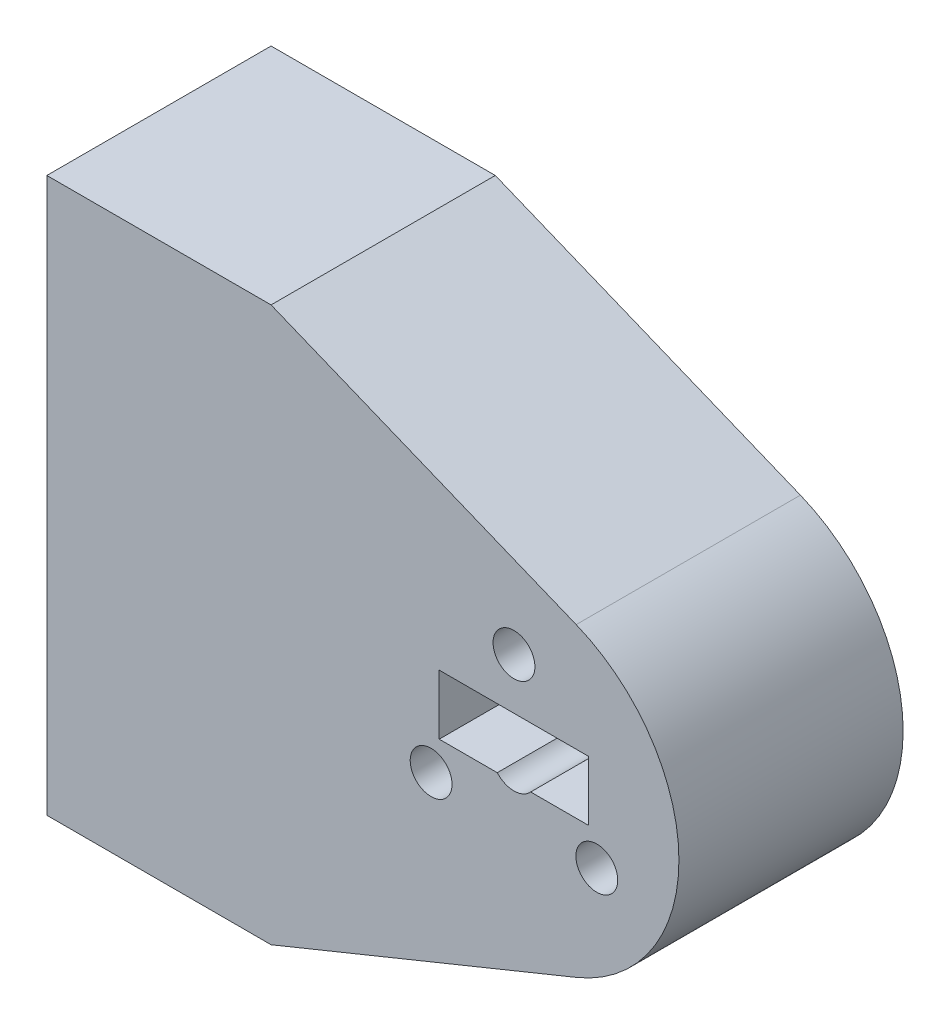
SolidWorks part; units mm, degrees
ref_plane "정면" through (0, 0, 0) normal (0, 0, 1) x (1, 0, 0)
ref_plane "윗면" through (0, 0, 0) normal (0, 1, 0) x (1, 0, 0)
ref_plane "우측면" through (0, 0, 0) normal (1, 0, 0) x (0, 0, -1)
sketch "스케치1" plane through (0, 0, 0) normal (0, 0, 1) x (1, 0, 0)
  line L0 (0, 0) -> (0, 33.5972) construction
  line L1 (0, 0) -> (-11.0851, -6.4) construction
  line L7 (10, 6) -> (-10, 6)
  line L8 (10, 6) -> (10, -2)
  line L9 (10, -2) -> (-10, -2)
  line L10 (-10, 6) -> (-10, -2)
  line L11 (10, 6) -> (-10, -2) construction
  line L12 (10, -2) -> (-10, 6) construction
  circle A0 centre (0, 0) radius 22.0716
  circle A1 centre (0, 12.8) radius 2.8
  circle A2 centre (0, 0) radius 15.95
  circle A3 centre (11.0851, -6.4) radius 2.8
  circle A4 centre (-11.0851, -6.4) radius 2.8
  circle A5 centre (0, 0) radius 3
  point P0 (0, 2)
  point P14 (0, 0)
  dimension "D1" = 5.6
  dimension "D2" = 31.9
  dimension "D3" = 44.1433
  dimension "D4" = 12.8
  dimension "D6" = 20
  dimension "D7" = 8
  dimension "D9" = 6
  dimension "D10" = 5.6
  dimension "D11" = 5.6
  dimension "D8" = 2
  dimension "D5" = 3
extrude "보스-돌출1" add sketch "스케치1" along normal blind 5 contours A1 A2 A4 A3 | A2 A0 region at (-21.4474, 0, 0) region at (-15.4989, 0, 0)
sketch "스케치2" plane through (0, 0, 0) normal (0, 0, 1) x (1, 0, 0)
  line L0 (0, 0) -> (-62.5, 0) construction
  line L1 (0, 22.0716) -> (-62.5, 22.0716)
  line L2 (-62.5, 22.0716) -> (-62.5, -22.0716)
  line L3 (-62.5, -22.0716) -> (0, -22.0716)
  line L4 (-45.5, 33.3049) -> (-45.5, -54.0151) construction
  line L5 (-62.5, -22.0716) -> (-62.5, -37.0716)
  line L6 (-62.5, -37.0716) -> (-32.5, -37.0716)
  line L7 (-32.5, -37.0716) -> (8.3266, -20.4408)
  line L8 (-45.5, -33.3049) -> (-45.5, 54.0151) construction
  line L9 (-32.5, 37.0716) -> (8.3266, 20.4408)
  line L10 (-62.5, 37.0716) -> (-32.5, 37.0716)
  line L11 (-62.5, 22.0716) -> (-62.5, 37.0716)
  line L12 (-10, 6) -> (-10, -2)
  line L13 (-10, 6) -> (-10, -2)
  line L14 (-2.2361, -2) -> (-10, -2)
  line L15 (-2.2361, -2) -> (-10, -2)
  line L16 (10, -2) -> (2.2361, -2)
  line L17 (10, -2) -> (2.2361, -2)
  line L18 (10, 6) -> (10, -2)
  line L19 (10, 6) -> (10, -2)
  line L20 (10, 6) -> (-10, 6)
  line L21 (10, 6) -> (-10, 6)
  circle A1 centre (0, 0) radius 22.0716
  circle A2 centre (0, 0) radius 22.0716
  circle A3 centre (0, 12.8) radius 2.8
  circle A4 centre (0, 12.8) radius 2.8
  circle A5 centre (-11.0851, -6.4) radius 2.8
  circle A6 centre (-11.0851, -6.4) radius 2.8
  arc A7 (-2.2361, -2) -> (2.2361, -2) centre (0, 0) ccw
  arc A8 (-2.2361, -2) -> (2.2361, -2) centre (0, 0) ccw
  circle A9 centre (11.0851, -6.4) radius 2.8
  circle A10 centre (11.0851, -6.4) radius 2.8
  point P12 (-45.5, 0)
  dimension "D5" = 15
  dimension "D6" = 30
  dimension "D2" = 44.1433
  dimension "D3" = 62.5
  dimension "D4" = 17
  dimension "D1" = 0
extrude "보스-돌출2" add sketch "스케치2" along normal blind 30 contours A2 L3 L5 L6 L7 | A2 L1 L2 L3 | A2 A10 A8 L15 L13 L21 L19 L17 A6 A4 | A2 L9 L10 L11 L1 region at (-39.6488, 0, 0) region at (-37.0594, 28.6096, 0) region at (4.1224, 21.0474, 0) region at (-37.0594, -28.6096, 0)
sketch "스케치3" plane through (0, 0, 0) normal (0, 0, 1) x (1, 0, 0)
  line L5 (-32.5, -37.0716) -> (8.3266, -20.4408)
  line L6 (-62.5, -37.0716) -> (-32.5, -37.0716)
  line L7 (-62.5, 37.0716) -> (-62.5, -37.0716)
  line L8 (-32.5, 37.0716) -> (-62.5, 37.0716)
  line L9 (8.3266, 20.4408) -> (-32.5, 37.0716)
  line L10 (-32.5, -37.0716) -> (8.3266, -20.4408)
  line L11 (-62.5, -37.0716) -> (-32.5, -37.0716)
  line L12 (-62.5, 37.0716) -> (-62.5, -37.0716)
  line L13 (-32.5, 37.0716) -> (-62.5, 37.0716)
  line L14 (8.3266, 20.4408) -> (-32.5, 37.0716)
  circle A0 centre (0, 12.8) radius 2.8
  arc A1 (8.3266, -20.4408) -> (8.3266, 20.4408) centre (0, 0) ccw
  arc A2 (8.3266, -20.4408) -> (8.3266, 20.4408) centre (0, 0) ccw
  circle A3 centre (0, 12.8) radius 2.8
  circle A4 centre (-11.0851, -6.4) radius 2.8
  circle A5 centre (-11.0851, -6.4) radius 2.8
  circle A6 centre (11.0851, -6.4) radius 2.8
  circle A7 centre (11.0851, -6.4) radius 2.8
  circle A8 centre (0, 12.8) radius 5
  circle A9 centre (11.0851, -6.4) radius 5
  circle A10 centre (-11.0851, -6.4) radius 5
  dimension "D2" = 10
  dimension "D3" = 10
  dimension "D4" = 10
  dimension "D1" = 0
extrude "컷-돌출1" cut sketch "스케치3" along normal blind 10 contours A9 A7 | A8 A3 | A10 A5 region at (-4.8586, 12.8, 0) region at (6.2265, -6.4, 0) region at (-15.9437, -6.4, 0)
fillet "필렛2" radius 2 4 edges at (8.7103, -2, 5) (10, -1.5192, 5) (10, -1.7596, 10) (9.3551, -2, 10)
fillet "필렛3" radius 2 4 edges at (-10, -1.5192, 5) (-10, -1.7596, 10) (-9.3551, -2, 10) (-8.7103, -2, 5)
sketch "스케치4" plane through (0, 37.0716, 0) normal (0, 1, 0) x (1, 0, 0)
  line L0 (-62.5, -15) -> (-32.5, -15) construction
  line L1 (-62.5, -30) -> (-62.5, 0) construction
  line L2 (-32.5, -30) -> (-32.5, 0) construction
  line L3 (-62.5, -15) -> (-45.5, -15) construction
  circle A0 centre (-45.5, -15) radius 2.5
  dimension "D2" = 5
  dimension "D1" = 17
